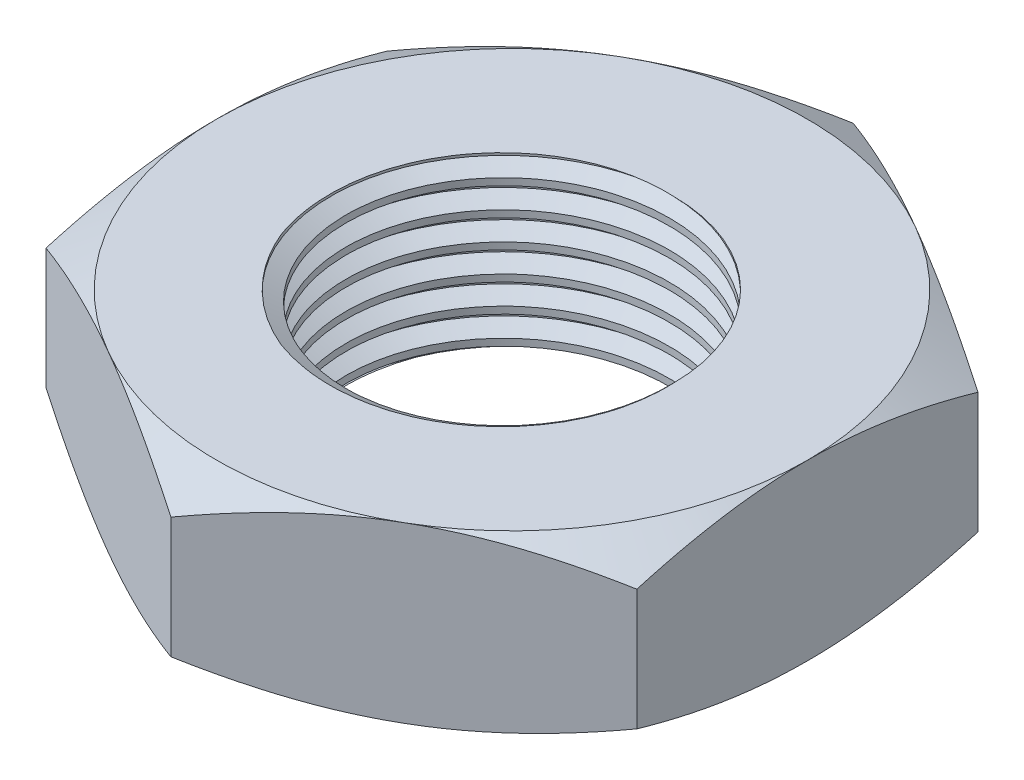
SolidWorks part; units mm, degrees
ref_plane "Front Plane" through (0, 0, 0) normal (0, 0, 1) x (1, 0, 0)
ref_plane "Top Plane" through (0, 0, 0) normal (0, 1, 0) x (1, 0, 0)
ref_plane "Right Plane" through (0, 0, 0) normal (1, 0, 0) x (0, 0, -1)
sketch "Sketch1" plane through (0, 0, 0) normal (0, 1, 0) x (1, 0, 0)
  line L0 (-4.65, 0) -> (4.65, 0) construction
  line L1 (-8.5, 4.9075) -> (-8.5, -4.9075)
  line L2 (-8.5, -4.9075) -> (0, -9.815)
  line L3 (0, -9.815) -> (8.5, -4.9075)
  line L4 (8.5, -4.9075) -> (8.5, 4.9075)
  line L5 (8.5, 4.9075) -> (0, 9.815)
  line L6 (0, 9.815) -> (-8.5, 4.9075)
  line L7 (0, 0) -> (0, 4.65) construction
  circle A0 centre (0, 0) radius 8.5 construction
  circle A1 centre (0, 0) radius 4.65 construction
  dimension "Thread Size" = 9.3
  dimension "Hex" = 17
extrude "Boss-Extrude1" add sketch "Sketch1" along normal mid plane 5
ref_plane "Plane2" through (0, 2.5, 0) normal (0, 1, 0) x (1, 0, 0)
sketch "Sketch10" plane through (0, 2.5, 0) normal (0, 1, 0) x (1, 0, 0)
  line L0 (0, 0) -> (0, 4.65) construction
  circle A0 centre (0, 0) radius 4.65 construction
  point P6 (0, 0)
hole_wizard "M5 Clearance Hole1" positions "3DSketch4" profile "Sketch11" hole size "M5" standard "ANSI Metric"
sketch3d "3DSketch4"
  point P0 (0, 2.5, 0)
sketch "Sketch11" plane through (0, 2.5, 0) normal (1, 0, 0) x (0, 0, 1)
  line L0 (0, 0) -> (0, 14.794)
  line L1 (0, 14.794) -> (4.65, 12)
  line L2 (4.65, 12) -> (4.65, 0)
  line L5 (4.65, 0) -> (0, 0)
  line L10 (0, 14.794) -> (-4.65, 12) construction
  line L11 (0, -6.35) -> (0, 107.95) construction
  dimension "Hole Dia." = 9.3
  dimension "Hole Depth" = 12
  dimension "Drill Angle" = 118
thread "Thread1" pitch 0.8 method cut profile "Thread Profile2" start angle 0, offset 1, length 0, pitch 0.8, diameter 9.3
ref_plane "Plane3" through (-4.65, 3.5, 0) normal (0, 0, 1) x (-1, 0, 0)
sketch "Thread Profile2" plane through (-4.65, 3.5, 0) normal (0, 0, 1) x (-1, 0, 0)
  line L0 (0, 0) -> (0, 0.8) construction
  line L1 (0, 0) -> (0.433, 0.25)
  line L2 (0.433, 0.25) -> (0.433, 0.35)
  line L3 (0.433, 0.35) -> (0, 0.6)
  line L4 (0.433, 0.3) -> (0, 0.3) construction
  line L11 (0, 0) -> (0, 0.6)
  point P2 (0, 0)
  dimension "Pitch" = 0.8
  dimension "Profile_Angle" = 60
  dimension "Profile_Land" = 0.1
  dimension "Profile_Height" = 0.433
sketch "Sketch5" plane through (0, 2.5, 0) normal (0, 1, 0) x (1, 0, 0)
  circle A0 centre (0, 0) radius 8.5 construction
  circle A1 centre (0, 0) radius 8.5
extrude "Cut-Extrude2" cut sketch "Sketch5" against normal through all draft 60 flip side to cut
mirror "Mirror1" about plane through (0, 0, 0) normal (0, 1, 0) of "Cut-Extrude2"
